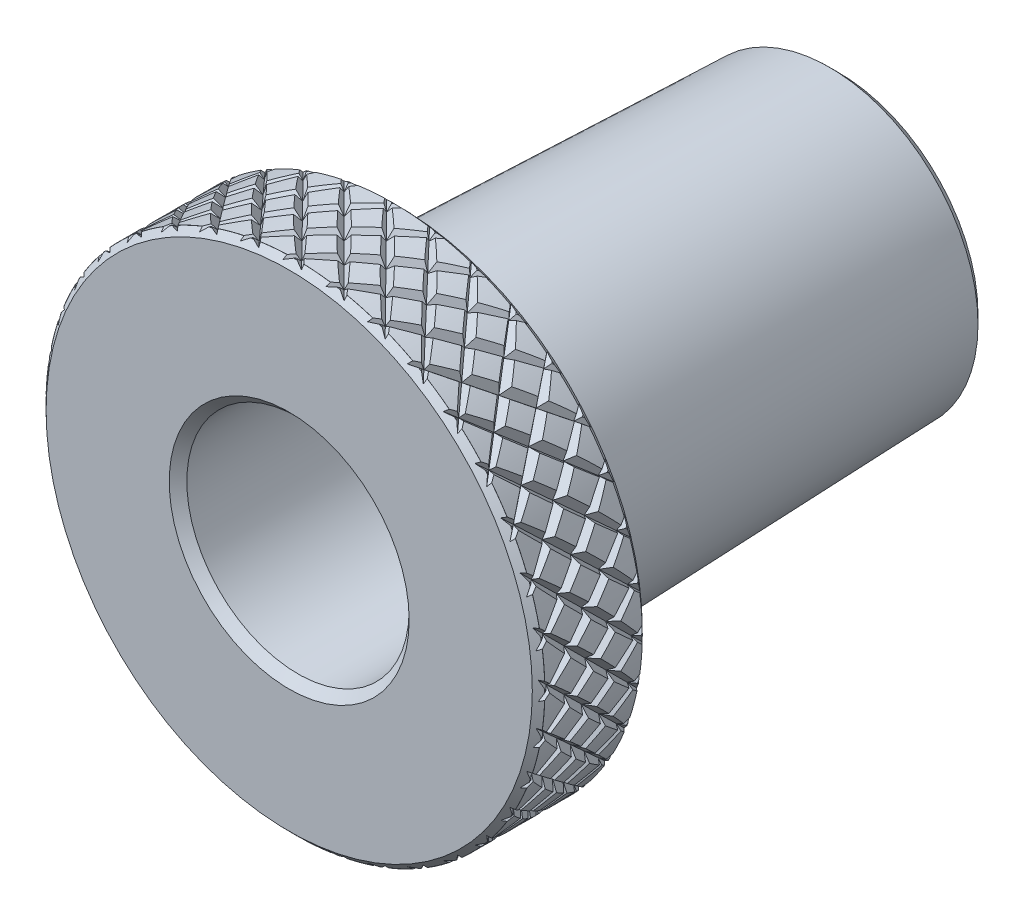
SolidWorks part; units mm, degrees
material "Nylon 101"
ref_plane "Front Plane" through (0, 0, 0) normal (0, 0, 1) x (1, 0, 0)
ref_plane "Top Plane" through (0, 0, 0) normal (0, 1, 0) x (1, 0, 0)
ref_plane "Right Plane" through (0, 0, 0) normal (1, 0, 0) x (0, 0, -1)
sketch "Sketch1" plane through (0, 0, 0) normal (0, 0, 1) x (1, 0, 0)
  circle A1 centre (-72.0725, 110.1243) radius 4.2824
extrude "Boss-Extrude1" add sketch "Sketch1" along normal blind 12.7 draft 2 draft outward yes
sketch "Sketch2" plane through (0, 0, 12.7) normal (0, 0, 1) x (1, 0, 0)
  circle A1 centre (-72.0725, 110.1243) radius 7.2072
extrude "Boss-Extrude2" add sketch "Sketch2" along normal blind 3.175
ref_plane "Plane2" through (-79.2797, 0, 0) normal (-1, 0, 0) x (0, 0, 1)
sketch "Sketch4" plane through (-79.2797, 0, 0) normal (1, 0, 0) x (0, 0, -1)
  line L0 (-14.2875, 117.3316) -> (-14.2875, 102.9171) construction
  line L1 (-12.7, 117.3316) -> (-15.875, 117.3316) construction
  line L2 (-15.875, 102.9171) -> (-12.7, 102.9171) construction
  line L3 (-17.3871, 113.2239) -> (-11.1879, 107.0248)
  point P11 (-14.2875, 110.1243)
  dimension "D1" = 45
fillet "Fillet1" radius 1.5875 1 edges at (-67.3466, 110.1243, 12.7)
sketch "Sketch3" plane through (0, 0, 15.875) normal (0, 0, 1) x (1, 0, 0)
  circle A0 centre (-72.0725, 110.1243) radius 3.2131
  dimension "D1" = 6.4262
extrude "Cut-Extrude1" cut sketch "Sketch3" against normal through all
ref_plane "Plane3" through (-79.2797, 113.2239, 17.3871) normal (0, -0.7071, -0.7071) x (-1, 0, 0)
sketch "Sketch7" plane through (-79.2797, 113.2239, 17.3871) normal (0, -0.7071, -0.7071) x (-1, 0, 0)
  line L0 (0, 0) -> (-0.254, 0) construction
  line L1 (-0.254, 0) -> (0, -0.1466)
  line L2 (0, -0.1466) -> (0, 0.1466)
  line L3 (0, 0.1466) -> (-0.254, 0)
  point P2 (0, 0)
  dimension "D1" = 0.254
sweep "Cut-Sweep2" cut profiles "Sketch7" path "Sketch4"
pattern_circular "CirPattern1" count 36 over 360 about axis through (-72.0725, 110.1243, 15.875) along (0, 0, -1) of "Cut-Sweep2"
ref_axis "Axis1" through (-72.0725, 110.1243, 0) along (0, 0, 1)
ref_plane "Plane4" through (-72.0725, 0, 0) normal (1, 0, 0) x (0, 0, -1)
mirror "Mirror1" about plane through (-72.0725, 0, 0) normal (1, 0, 0) of "CirPattern1"
sketch "Sketch8" plane through (-72.0725, 0, 0) normal (1, 0, 0) x (0, 0, -1)
  line L0 (-15.875, 117.3292) -> (-12.7, 117.3206) construction
  line L1 (-15.875, 117.3316) -> (-15.875, 117.3267) construction
  line L2 (-12.7, 115.8921) -> (-12.7, 116.1581) construction
  line L3 (-15.875, 117.3292) -> (-15.875, 117.1493) construction
  line L4 (-15.875, 117.1493) -> (-15.6952, 117.3287)
  line L5 (-15.6952, 117.3287) -> (-15.875, 117.3292) construction
  line L6 (-14.2875, 117.3249) -> (-14.2875, 110.1134) construction
  line L7 (-12.8798, 117.3287) -> (-12.7, 117.3292) construction
  line L8 (-12.7, 117.3292) -> (-12.7, 117.1493) construction
  line L9 (-12.573, 117.1493) -> (-12.7, 117.1493)
  line L10 (-15.6952, 117.3287) -> (-15.6952, 117.3606)
  line L11 (-15.6952, 117.3606) -> (-16.002, 117.3606)
  line L12 (-16.002, 117.3606) -> (-16.002, 117.1493)
  line L13 (-16.002, 117.1493) -> (-15.875, 117.1493)
  line L14 (-12.573, 117.3606) -> (-12.573, 117.1493)
  line L15 (-12.8798, 117.3606) -> (-12.573, 117.3606)
  line L16 (-12.8798, 117.3287) -> (-12.8798, 117.3606)
  line L17 (-12.7, 117.1493) -> (-12.8798, 117.3287)
  ellipse E0 centre (-8.6102, 110.1243) end of major axis (0.2213, 104.8038) minor radius 5.6759 (-12.7, 117.3206) -> (-13.0193, 117.3306) ccw construction
  dimension "D1" = 0.254
  dimension "D2" = 0.254
revolve "Cut-Revolve1" cut sketch "Sketch8" angle 360 about axis through (-72.0725, 110.1243, 0) along (0, 0, 1)
chamfer "Chamfer2" distance 0.254 angle 45 3 edges at (-68.8594, 110.1243, 0) (-67.7901, 110.1243, 0) (-68.8594, 110.1243, 15.875) first distance on face at (-68.8594, 110.1243, 0) first distance on face at (-68.8594, 110.1243, 15.875)
